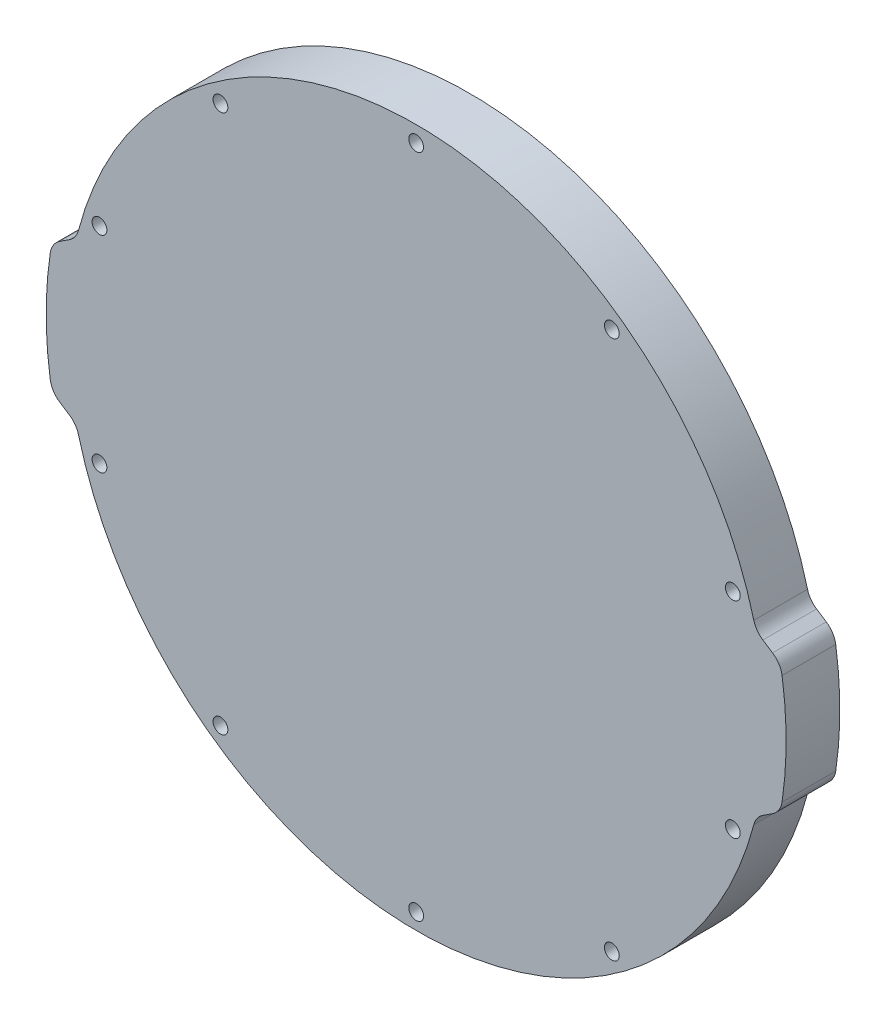
SolidWorks part; units mm, degrees
material "Acrylic (Medium-high impact)"
ref_plane "Front Plane" through (0, 0, 0) normal (0, 0, 1) x (1, 0, 0)
ref_plane "Top Plane" through (0, 0, 0) normal (0, 1, 0) x (1, 0, 0)
ref_plane "Right Plane" through (0, 0, 0) normal (1, 0, 0) x (0, 0, -1)
sketch "Sketch1" plane through (0, 0, 0) normal (0, 0, 1) x (1, 0, 0)
  line L0 (-87.5, 0) -> (87.5, 0) construction
  line L1 (0, -87.5) -> (0, 87.5) construction
  line L2 (-86.1626, 15.24) -> (-80.3219, 19.05)
  line L3 (86.1626, 15.24) -> (80.3219, 19.05)
  line L4 (-86.1626, -15.24) -> (-80.3219, -19.05)
  line L5 (86.1626, -15.24) -> (80.3219, -19.05)
  line L6 (0, 0) -> (24.6341, 33.9059) construction
  line L7 (0, 0) -> (-24.6341, 33.9059) construction
  arc A0 (-86.1626, 15.24) -> (-86.1626, -15.24) centre (0, 0) ccw
  arc A1 (-80.3219, 19.05) -> (-80.3219, -19.05) centre (0, 0) ccw construction
  circle A2 centre (0, 0) radius 78.74 construction
  circle A5 centre (0, 78.74) radius 1.75
  circle A10 centre (46.2822, 63.702) radius 1.75
  circle A11 centre (74.8862, 24.332) radius 1.75
  circle A12 centre (74.8862, -24.332) radius 1.75
  circle A13 centre (46.2822, -63.702) radius 1.75
  circle A14 centre (0, -78.74) radius 1.75
  circle A15 centre (-46.2822, -63.702) radius 1.75
  circle A16 centre (-74.8862, -24.332) radius 1.75
  circle A17 centre (-74.8862, 24.332) radius 1.75
  circle A18 centre (-46.2822, 63.702) radius 1.75
  arc A19 (86.1626, 15.24) -> (-86.1626, 15.24) centre (0, 0) ccw construction
  arc A20 (86.1626, -15.24) -> (86.1626, 15.24) centre (0, 0) ccw
  arc A21 (-86.1626, -15.24) -> (86.1626, -15.24) centre (0, 0) ccw construction
  arc A22 (80.3219, 19.05) -> (-80.3219, 19.05) centre (0, 0) ccw
  arc A23 (80.3219, -19.05) -> (80.3219, 19.05) centre (0, 0) ccw construction
  arc A24 (-80.3219, -19.05) -> (80.3219, -19.05) centre (0, 0) ccw
  circle A25 centre (0, 0) radius 63.5 construction
  circle A26 centre (0, 0) radius 41.91 construction
  circle A27 centre (24.6341, 33.9059) radius 5.08
  circle A28 centre (-24.6341, 33.9059) radius 5.08
  dimension "D2" = 157.48
  dimension "D3" = 165.1
  dimension "D4" = 175
  dimension "D5" = 3.5
  dimension "D6" = 127
  dimension "D7" = 10.16
  dimension "D12" = 83.82
  dimension "D9" = 19.05
  dimension "D10" = 15.24
  dimension "D11" = 72
  dimension "D8" = 10
extrude "Boss-Extrude1" add sketch "Sketch1" along normal mid plane 12.7 contours A28 | L4 A24 L5 A20 L3 A22 L2 A0 A18 A17 A16 A15 A14 A13 A12 A11 A10 A5 A27 A28 | A27 region at (0, -0.2558, 0) region at (-24.6341, 33.9059, 0)
fillet "Fillet1" radius 5.08 8 edges at (-86.1626, 15.24, 0) (-80.3219, 19.05, 0) (-86.1626, -15.24, 0) (-80.3219, -19.05, 0) (86.1626, -15.24, 0) (80.3219, -19.05, 0) (86.1626, 15.24, 0) (80.3219, 19.05, 0)
